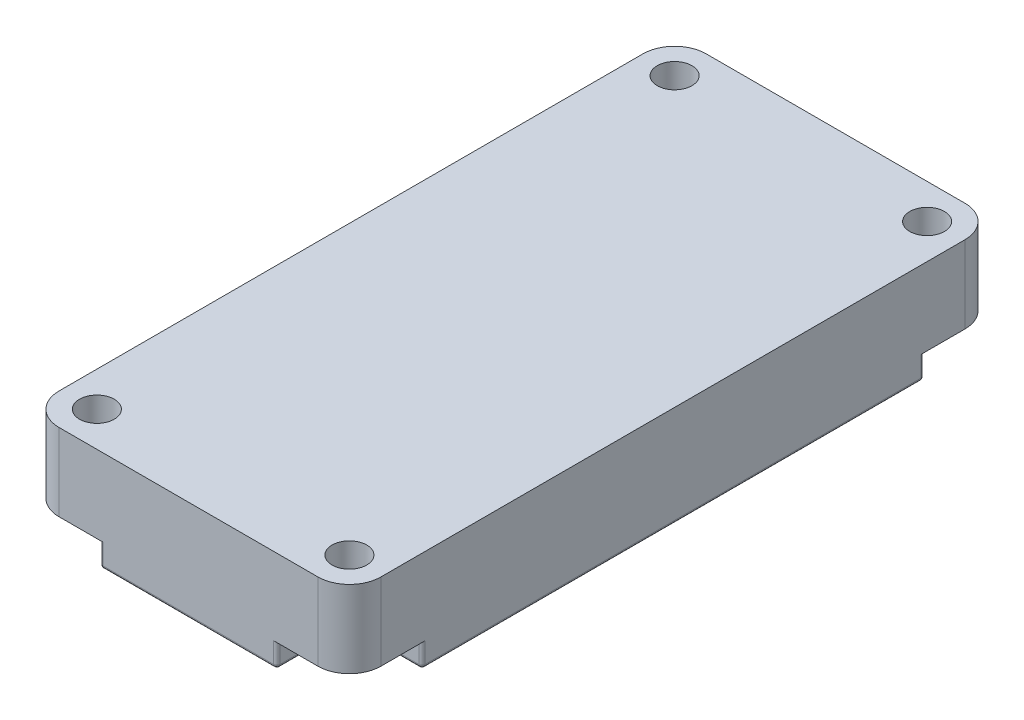
SolidWorks part; units mm, degrees
material "Polyethylene Cross-Linked"
ref_plane "Front Plane" through (0, 0, 0) normal (0, 0, 1) x (1, 0, 0)
ref_plane "Top Plane" through (0, 0, 0) normal (0, 1, 0) x (1, 0, 0)
ref_plane "Right Plane" through (0, 0, 0) normal (1, 0, 0) x (0, 0, -1)
sketch "Sketch1" plane through (0, 0, 0) normal (0, 1, 0) x (1, 0, 0)
  line L1 (-10.2, 20.5) -> (10.2, 20.5)
  line L2 (-10.2, 20.5) -> (-10.2, -20.5)
  line L3 (-10.2, -20.5) -> (10.2, -20.5)
  line L4 (10.2, 20.5) -> (10.2, -20.5)
  line L5 (-10.2, 20.5) -> (10.2, -20.5) construction
  line L6 (-10.2, -20.5) -> (10.2, 20.5) construction
  point P0 (0, 0)
  dimension "D1" = 20.4
  dimension "D2" = 41
extrude "Boss-Extrude1" add sketch "Sketch1" against normal blind 6.4
sketch "Sketch2" plane through (0, -6.4, 0) normal (0, -1, 0) x (-1, 0, 0)
  line L0 (5.6, -17.7) -> (5.6, -20.5)
  line L1 (10.2, -20.5) -> (-10.2, -20.5) construction
  line L2 (7.4, -15.9) -> (10.2, -15.9)
  line L3 (10.2, 20.5) -> (10.2, -20.5) construction
  line L4 (5.6, -20.5) -> (10.2, -20.5)
  line L5 (10.2, -20.5) -> (10.2, -15.9)
  arc A0 (7.4, -15.9) -> (5.6, -17.7) centre (7.4, -17.7) ccw
  dimension "D3" = 3.6
  dimension "D1" = 4.6
  dimension "D2" = 4.6
extrude "Cut-Extrude1" cut sketch "Sketch2" against normal blind 1.5
hole_wizard "M2 Clearance Hole1" positions "Sketch8" profile "Sketch7" hole size "M2" standard "ANSI Metric" end condition through all
sketch "Sketch8" plane through (0, -4.9, 0) normal (0, -1, 0) x (-1, 0, 0)
  line L0 (10.2, -20.5) -> (10.2, -15.9) construction
  line L1 (5.6, -20.5) -> (10.2, -20.5) construction
  point P0 (8, -18.3)
  dimension "D1" = 2.2
  dimension "D2" = 2.2
sketch "Sketch7" plane through (-8, -4.9, 18.3) normal (1, 0, 0) x (0, 0, -1)
  line L0 (0, 0) -> (0, 4.9)
  line L1 (0, 4.9) -> (1.1, 4.9)
  line L2 (1.1, 4.9) -> (1.1, 0)
  line L5 (1.1, 0) -> (0, 0)
  line L11 (0, -6.35) -> (0, 107.95) construction
  dimension "Thru Hole Dia." = 2.2
  dimension "Thru Hole Depth" = 4.9
mirror "Mirror1" about plane through (0, 0, 0) normal (1, 0, 0) of "M2 Clearance Hole1", "Cut-Extrude1"
mirror "Mirror2" about plane through (0, 0, 0) normal (0, 0, 1) of "Mirror1", "Cut-Extrude1"
sketch "Sketch3" plane through (0, 0, 0) normal (0, 0, 1) x (1, 0, 0)
  line L0 (10.2, -3.4) -> (10.2, -6.4)
  line L1 (10.2, -4.9) -> (10.2, 0) construction
  line L2 (10.2, -6.4) -> (9.1081, -6.4)
  line L3 (10.2, -6.4) -> (7.4, -6.4) construction
  line L4 (9.1081, -6.4) -> (10.2, -3.4)
  dimension "D1" = 3
  dimension "D2" = 20
sketch "Sketch4" plane through (0, 0, 0) normal (1, 0, 0) x (0, 0, -1)
  line L0 (20.5, -3.4) -> (19.4081, -6.4)
  line L1 (20.5, -4.9) -> (20.5, 0) construction
  line L2 (17.7, -6.4) -> (20.5, -6.4) construction
  line L3 (19.4081, -6.4) -> (20.5, -6.4)
  line L4 (20.5, -6.4) -> (20.5, -3.4)
  dimension "D1" = 3
  dimension "D2" = 20
fillet "Fillet1" radius 0.2 16 edges at (5.6, -6.4, -19.1) (0, -6.4, -20.5) (-5.6, -6.4, -19.1) (-6.1272, -6.4, -16.4272) (-8.8, -6.4, -15.9) (-10.2, -6.4, 0) (-8.8, -6.4, 15.9) (-6.1272, -6.4, 16.4272) (-5.6, -6.4, 19.1) (0, -6.4, 20.5) (5.6, -6.4, 19.1) (6.1272, -6.4, 16.4272) (8.8, -6.4, 15.9) (10.2, -6.4, 0) (8.8, -6.4, -15.9) (6.1272, -6.4, -16.4272)
fillet "Fillet2" radius 0.2 16 edges at (5.5414, -6.3414, -20.4414) (-5.5414, -6.3414, -20.4414) (-10.1414, -6.3414, 15.8414) (-5.5414, -6.3414, 20.4414) (5.5414, -6.3414, 20.4414) (10.1414, -6.3414, 15.8414) (10.1414, -6.3414, -15.8414) (-10.1414, -6.3414, -15.8414) (5.6, -5.55, -20.5) (-5.6, -5.55, -20.5) (-10.2, -5.55, 15.9) (-5.6, -5.55, 20.5) (5.6, -5.55, 20.5) (10.2, -5.55, 15.9) (10.2, -5.55, -15.9) (-10.2, -5.55, -15.9)
fillet "Fillet3" radius 2 4 edges at (10.2, -2.45, 20.5) (-10.2, -2.45, 20.5) (10.2, -2.45, -20.5) (-10.2, -2.45, -20.5)
